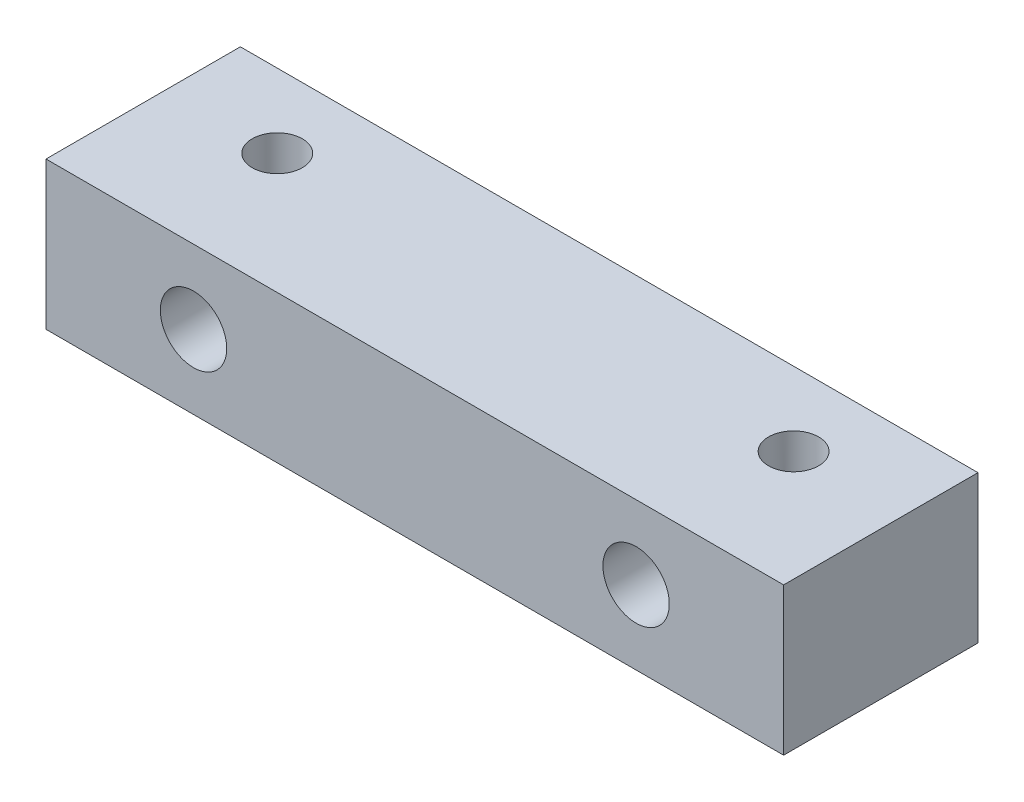
SolidWorks part; units mm, degrees
ref_plane "Front Plane" through (0, 0, 0) normal (0, 0, 1) x (1, 0, 0)
ref_plane "Top Plane" through (0, 0, 0) normal (0, 1, 0) x (1, 0, 0)
ref_plane "Right Plane" through (0, 0, 0) normal (1, 0, 0) x (0, 0, -1)
sketch "Sketch1" plane through (0, 0, 0) normal (0, 0, 1) x (1, 0, 0)
  line L1 (-25, -5) -> (25, -5)
  line L2 (-25, -5) -> (-25, 5)
  line L3 (-25, 5) -> (25, 5)
  line L4 (25, -5) -> (25, 5)
  line L5 (-25, -5) -> (25, 5) construction
  line L6 (-25, 5) -> (25, -5) construction
  point P0 (0, 0)
  dimension "D1" = 50
  dimension "D2" = 10
extrude "Boss-Extrude1" add sketch "Sketch1" along normal blind 13.175
hole_wizard "CBORE for M3 SHCS2" positions "Sketch8" profile "Sketch9" counterbore size "M3" standard "ANSI Metric" end condition through all
sketch "Sketch8" plane through (0, -5, 0) normal (0, -1, 0) x (-1, 0, 0)
  line L0 (-17.5, -5) -> (17.5, -5)
  line L1 (25, 0) -> (-25, 0) construction
  point P0 (-17.5, -5)
  point P2 (17.5, -5)
  point P9 (0, -5)
  dimension "D1" = 35
  dimension "D2" = 5
sketch "Sketch9" plane through (17.5, -5, 5) normal (1, 0, 0) x (0, 0, -1)
  line L0 (0, 0) -> (0, 10)
  line L1 (0, 10) -> (1.7, 10)
  line L3 (1.7, 10) -> (1.7, 5)
  line L4 (1.7, 5) -> (3.25, 5)
  line L5 (3.25, 5) -> (3.25, 0)
  line L7 (3.25, 0) -> (0, 0)
  line L11 (0, -6.35) -> (0, 107.95) construction
  dimension "Thru Hole Dia." = 3.4
  dimension "Thru Hole Depth" = 10
  dimension "C'Bore Dia." = 6.5
  dimension "C'Bore Depth" = 5
hole_wizard "M4 Clearance Hole1" positions "Sketch10" profile "Sketch11" hole size "M4" standard "ANSI Metric" end condition through all
sketch "Sketch10" plane through (0, 0, 0) normal (0, 0, -1) x (-1, 0, 0)
  line L0 (-15, 0) -> (15, 0)
  point P0 (-15, 0)
  point P1 (15, 0)
  point P8 (0, 0)
  dimension "D1" = 30
sketch "Sketch11" plane through (15, 0, 0) normal (1, 0, 0) x (0, 1, 0)
  line L0 (0, 0) -> (0, 13.175)
  line L1 (0, 13.175) -> (2.25, 13.175)
  line L2 (2.25, 13.175) -> (2.25, 0)
  line L5 (2.25, 0) -> (0, 0)
  line L11 (0, -6.35) -> (0, 107.95) construction
  dimension "Thru Hole Dia." = 4.5
  dimension "Thru Hole Depth" = 13.175
